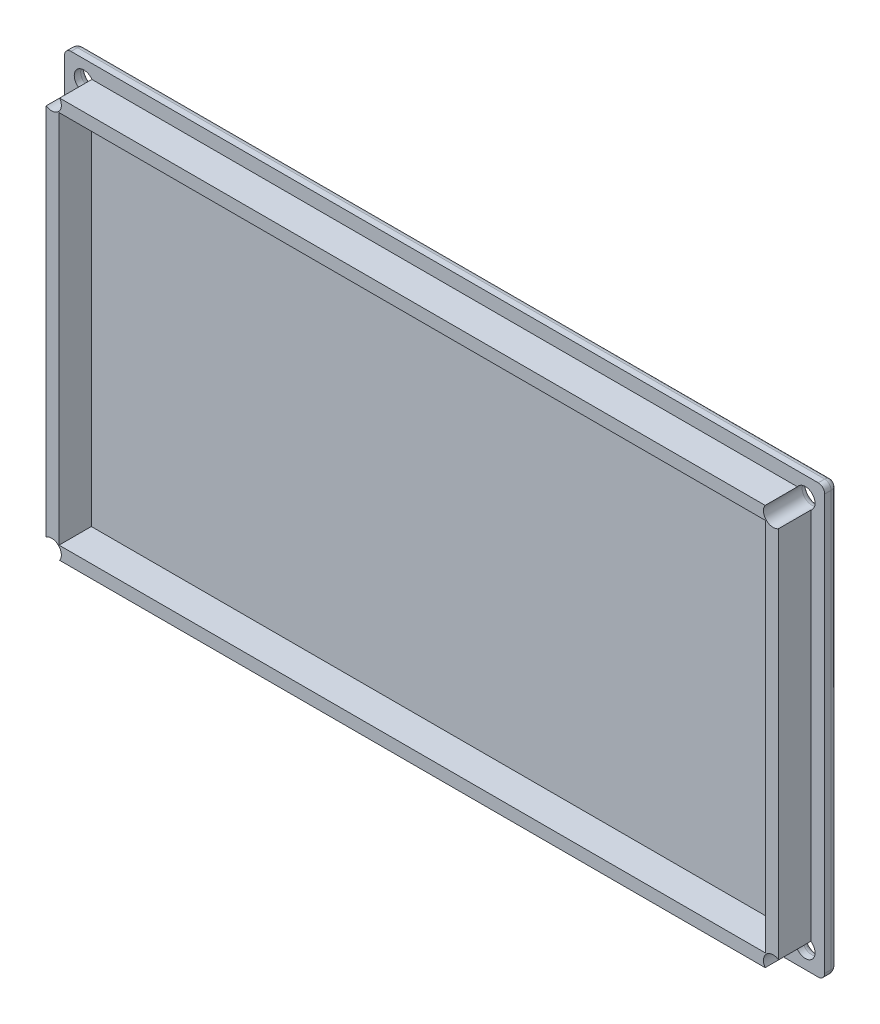
SolidWorks part; units mm, degrees
ref_plane "Front Plane" through (0, 0, 0) normal (0, 0, 1) x (1, 0, 0)
ref_plane "Top Plane" through (0, 0, 0) normal (0, 1, 0) x (1, 0, 0)
ref_plane "Right Plane" through (0, 0, 0) normal (1, 0, 0) x (0, 0, -1)
sketch "Sketch1" plane through (0, 0, 0) normal (0, 0, 1) x (1, 0, 0)
  line L1 (-55.6979, 33.2) -> (62.2021, 33.2)
  line L2 (-55.6979, 33.2) -> (-55.6979, -33.2)
  line L3 (-55.6979, -33.2) -> (62.2021, -33.2)
  line L4 (62.2021, 33.2) -> (62.2021, -33.2)
  line L5 (-55.6979, 33.2) -> (62.2021, -33.2) construction
  line L6 (-55.6979, -33.2) -> (62.2021, 33.2) construction
  point P0 (3.2521, 0)
  dimension "D1" = 66.4
  dimension "D2" = 117.9
extrude "Boss-Extrude1" add sketch "Sketch1" along normal blind 2
sketch "Sketch2" plane through (0, 0, 2) normal (0, 0, 1) x (1, 0, 0)
  line L0 (60.0521, -31.05) -> (60.0521, 31.05)
  line L1 (60.0521, 31.05) -> (-53.5479, 31.05)
  line L2 (-53.5479, 31.05) -> (-53.5479, -31.05)
  line L3 (-53.5479, -31.05) -> (60.0521, -31.05)
  line L12 (58.0521, -29.05) -> (58.0521, 29.05)
  line L13 (58.0521, 29.05) -> (-51.5479, 29.05)
  line L14 (-51.5479, 29.05) -> (-51.5479, -29.05)
  line L15 (-51.5479, -29.05) -> (58.0521, -29.05)
  line L16 (62.2021, 33.2) -> (-55.6979, 33.2) construction
  line L17 (-55.6979, 33.2) -> (-55.6979, -33.2) construction
  line L18 (-55.6979, -33.2) -> (62.2021, -33.2) construction
  line L19 (62.2021, -33.2) -> (62.2021, 33.2) construction
  dimension "D1" = 2.15
  dimension "D2" = 2.15
  dimension "D4" = 2.15
  dimension "D5" = 2.15
  dimension "D3" = 2
extrude "Boss-Extrude2" add sketch "Sketch2" along normal blind 5
sketch "Sketch3" plane through (0, 0, 0) normal (0, 0, -1) x (-1, 0, 0)
  line L0 (-62.2021, 33.2) -> (55.6979, 33.2) construction
  line L5 (-62.2021, -33.2) -> (-62.2021, 33.2) construction
  circle A0 centre (-59.2021, 30.2) radius 1.5
  dimension "D3" = 3
  dimension "D1" = 3
  dimension "D2" = 3
extrude "Cut-Extrude2" cut sketch "Sketch3" against normal through all both and the other way through all
mirror "Mirror2" about plane through (0, 0, 0) normal (0, 1, 0) of "Cut-Extrude2"
sketch "Sketch4" plane through (0, 0, 0) normal (0, 0, -1) x (-1, 0, 0)
  line L0 (-3.2521, 33.2) -> (-3.2521, -33.2) construction
  line L1 (-62.2021, 33.2) -> (55.6979, 33.2) construction
  line L2 (55.6979, -33.2) -> (-62.2021, -33.2) construction
  line L3 (-62.2021, 0) -> (55.6979, 0) construction
  line L4 (-62.2021, -33.2) -> (-62.2021, 33.2) construction
  line L5 (55.6979, 33.2) -> (55.6979, -33.2) construction
  dimension "D1" = 58.95
ref_plane "Plane1" through (3.2521, 0, 0) normal (1, 0, 0) x (0, 0, -1)
mirror "Mirror3" about plane through (0, 0, 0) normal (0, 1, 0) of "Cut-Extrude2" second plane through (3.2521, 0, 0) second plane normal (1, 0, 0)
fillet "Fillet1" radius 1 4 edges at (62.2021, -33.2, 1) (62.2021, 33.2, 1) (-55.6979, 33.2, 1) (-55.6979, -33.2, 1)
fillet "Fillet2" radius 1 12 edges at (62.2021, 0, 0) (3.2521, -33.2, 0) (-55.6979, 0, 0) (3.2521, 33.2, 0) (-55.405, -32.9071, 0) (-55.405, 32.9071, 0) (61.9092, 32.9071, 0) (61.9092, -32.9071, 0) (60.7021, 30.2, 0) (60.7021, -30.2, 0) (-51.1979, 30.2, 0) (-51.1979, -30.2, 0)
